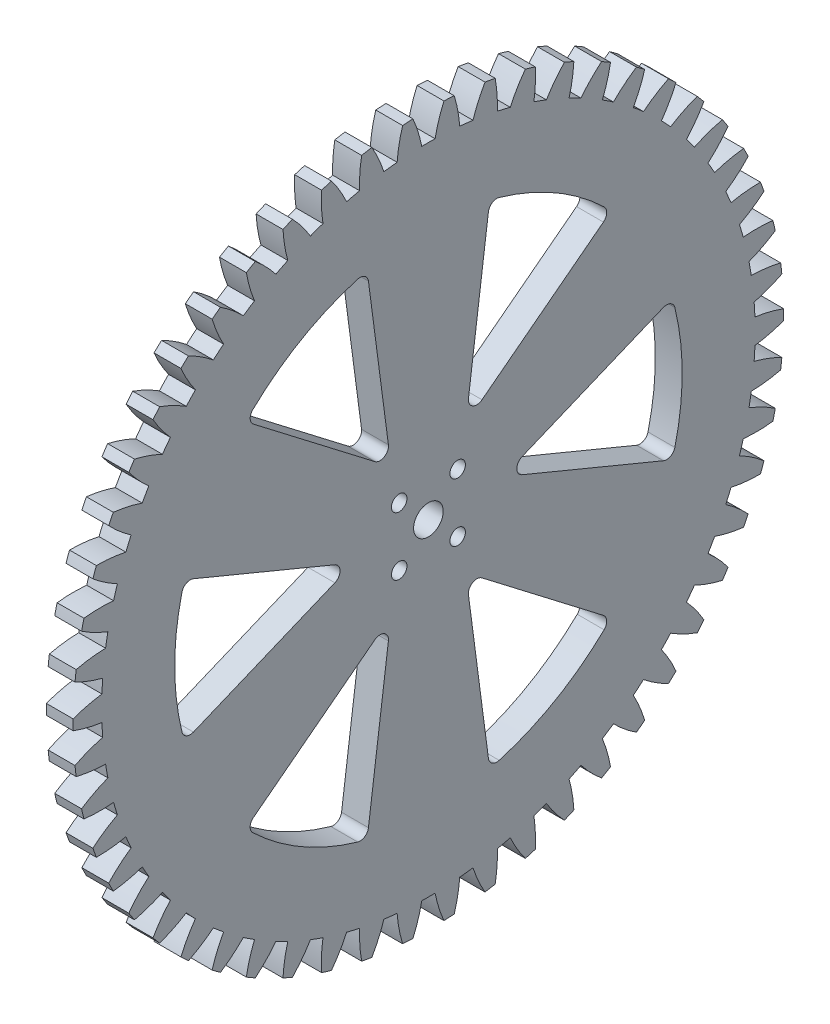
SolidWorks part; units mm, degrees
ref_plane "Plane1" through (0, 0, 0) normal (0, 0, 1) x (1, 0, 0)
ref_plane "Plane2" through (0, 0, 0) normal (0, 1, 0) x (1, 0, 0)
ref_plane "Plane3" through (0, 0, 0) normal (1, 0, 0) x (0, 0, -1)
sketch "HoldingSke" plane through (0, 0, 0) normal (0, 1, 0) x (1, 0, 0)
  line L0 (0, 0) -> (0.1959, -0.2697)
  line L1 (-15, 0) -> (100, 0) construction
  line L2 (0, 0) -> (-2.1039, 2.3779)
  line L3 (0, 0) -> (-11.863, 4.5341)
  line L4 (0, 0) -> (5.0761, 6.9867)
  line L5 (0, 0) -> (-46.8476, -17.4728)
  line L6 (0, 0) -> (-5.2639, -3.5516)
  line L7 (-2.1039, 2.3779) -> (8.6586, 51.2059)
  line L8 (-76.2, 54.61) -> (-75.2, 54.61)
  line L9 (-67.7845, 28.3722) -> (-49.3413, 33.142)
  line L10 (-76.2, 71.12) -> (104.1128, 71.12)
  line L11 (0, 0) -> (-6.35, 0)
  line L12 (-76.2, 101.6) -> (-76.093, 101.6)
  line L13 (24.9733, 27.94) -> (52.9518, 28.4284)
  line L14 (24.9733, 27.94) -> (24.9743, 27.94)
  line L15 (24.9733, 27.94) -> (100.4006, 29.5858)
  line L16 (-63.627, -3) -> (-12.827, -3)
  circle A0 centre (0, 0) radius 3.5
  circle A1 centre (0, 0) radius 37.5
  circle A2 centre (0, 0) radius 37.5
  circle A3 centre (0, 0) radius 3.5
  dimension "Num_teeth" = 54
  dimension "Pitch_radius" = 180.3128
  dimension "Width" = 6.35
  dimension "Thickness" = 6.35
sketch "BasProSke" plane through (0, 0, 0) normal (0, 1, 0) x (1, 0, 0)
  line L0 (-10, 0) -> (60, 0) construction
  line L1 (0, 0) -> (0, 84)
  line L2 (0, 0) -> (6.35, 0)
  line L3 (6.35, 0) -> (6.35, 84)
  line L4 (6.35, 84) -> (0, 84)
  dimension "Thickness" = 6.35
  dimension "Diameter" = 168
revolve "Base-Revolve" add sketch "BasProSke" angle 360 about L0
sketch "TooCutSke" plane through (0, 0, 0) normal (1, 0, 0) x (0, 0, -1)
  line L1 (0, 0) -> (0, 107) construction
  line L2 (0, 0) -> (-2.5431, 80.9601) construction
  line L3 (0, 0) -> (-9.4161, 161.6679) construction
  line L4 (-2.5431, 80.9601) -> (-4.708, 80.834) construction
  arc A0 (1.5754, 77.2329) -> (-1.5754, 77.2329) centre (0, 0) ccw
  arc A1 (3.6761, 83.9449) -> (-3.6761, 83.9449) centre (0, 0) ccw
  circle A2 centre (0, 0) radius 81 construction
  circle A3 centre (0, 0) radius 78.42 construction
  arc A4 (-1.5754, 77.2329) -> (-3.6761, 83.9449) centre (-33.364, 70.9685) ccw
  arc A5 (3.6761, 83.9449) -> (1.5754, 77.2329) centre (33.364, 70.9685) ccw
extrude "ToothCut" cut sketch "TooCutSke" along normal through all
fillet "Breaks" [suppressed] radius 0.06 tangent propagation no
fillet "RootFillets" [suppressed] radius 0.751
pattern_circular "TeethCuts" count 54 every 6.667 about axis through (-10, 0, 0) along (1, 0, 0) of "ToothCut", "RootFillets", "Breaks"
sketch "HubNeaOneSke" plane through (0, 0, 0) normal (-1, 0, 0) x (0, 0, 1)
  circle A0 centre (0, 0) radius 37.5
  dimension "Diameter" = 75
extrude "HubNearOne" [suppressed] add sketch "HubNeaOneSke" along normal blind 43.6501
sketch "HubNeaBotSke" plane through (0, 0, 0) normal (-1, 0, 0) x (0, 0, 1)
  circle A0 centre (0, 0) radius 37.5
  dimension "Diameter" = 75
extrude "HubNearBoth" [suppressed] add sketch "HubNeaBotSke" along normal blind 21.825
ref_plane "FarPln" through (6.35, 0, 0) normal (1, 0, 0) x (0, 0, -1)
sketch "HubFarSke" plane through (6.35, 0, 0) normal (1, 0, 0) x (0, 0, -1)
  circle A0 centre (0, 0) radius 37.5
  dimension "Diameter" = 75
extrude "HubFar" [suppressed] add sketch "HubFarSke" along normal blind 21.825
sketch "BorSke" plane through (0, 0, 0) normal (1, 0, 0) x (0, 0, -1)
  circle A0 centre (0, 0) radius 3.5
  dimension "Diameter" = 7
extrude "Bore" cut sketch "BorSke" along normal mid plane 100.0001
sketch "KeySke" plane through (0, 0, 0) normal (1, 0, 0) x (0, 0, -1)
  line L0 (-1, 0) -> (-1, 4.5)
  line L1 (-1, 4.5) -> (1, 4.5)
  line L2 (1, 4.5) -> (1, 0)
  line L3 (0, 0) -> (0, 34) construction
  line L4 (-1, 0) -> (1, 0)
  dimension "Width" = 2
extrude "Keyway" [suppressed] cut sketch "KeySke" along normal mid plane 100.0001
pattern_circular "Keyway2" [suppressed] count 2 every 90 about axis through (-10, 0, 0) along (1, 0, 0) reverse direction yes
sketch "Esquisse1" plane through (0, 0, 0) normal (-1, 0, 0) x (0, 0, 1)
  circle A0 centre (6.9148, 6.9148) radius 1.83
  point P2 (6.9148, 6.9148)
  dimension "D1" = 3.66
extrude "Enlèv. mat.-Extru.1" cut sketch "Esquisse1" against normal up to next
pattern_circular "Répétition circulaire1" count 4 every 90 about axis through (0, 0, 0) along (-1, 0, 0) of "Enlèv. mat.-Extru.1"
sketch "Esquisse2" plane through (0, 0, 0) normal (-1, 0, 0) x (0, 0, 1)
  line L0 (17.667, 0) -> (57.667, 16.5685)
  line L1 (17.667, 0) -> (57.667, -16.5685)
  line L2 (50, 0) -> (-50, 0) construction
  arc A0 (57.667, -16.5685) -> (57.667, 16.5685) centre (0, 0) ccw
  point P5 (16.15, 0)
  point P7 (11.6683, 0)
  point P10 (50.8815, -40.4484)
  point P11 (60.648, -23.3842)
  dimension "D2" = 120
  dimension "D1" = 40
  dimension "D3" = 45
extrude "Enlèv. mat.-Extru.2" cut sketch "Esquisse2" against normal up to next
fillet "Congé1" radius 2 3 edges at (3.175, 0, 17.667) (3.175, -16.5685, 57.667) (3.175, 16.5685, 57.667)
pattern_circular "Répétition circulaire2" count 6 over 360 about axis through (0, 0, 0) along (-1, 0, 0) of "Enlèv. mat.-Extru.2", "Congé1"
equation "' \"Module@HoldingSke\" = 6.35"
equation "' \"Num_teeth@HoldingSke\" = 12"
equation "' \"Ap@HoldingSke\" =  20"
equation "' \"Ap@HoldingSke\" = 20"
equation "' \"Width@HoldingSke\" = 0.5 * 25.4"
equation "' \"Hub_dia@HoldingSke\"= 1 * 25.4"
equation "' \"Hub_dia@HoldingSke\" = 1 * 25.4"
equation "' \"Overall_len@HoldingSke\" = 1.0 * 25.4"
equation "' \"Bore@HoldingSke\" = 0.75 * 25.4"
equation "' \"T_dim@HoldingSke\" = 0.1 * 25.4"
equation "' \"Width@KeySke\" = 0.25 * 25.4"
equation "' \"Show_teeth@HoldingSke\" = 13"
equation "' \"Backlash@HoldingSke\" = 0.009 * 25.4"
equation "' \"Addendum_fac@HoldingSke\" = 1.0"
equation "' \"Dedendum_fac@HoldingSke\" = 1.25"
equation "' \"Dedendum_add@HoldingSke\" = 0.00005 * 25.4"
equation "' \"Clearance_fac@HoldingSke\" = 0.25"
equation "\"Pitch@HoldingSke\" = 1 / \"Module@HoldingSke\""
equation "\"Overcut_dia@TooCutSke\" = (\"Num_teeth@HoldingSke\" + 2 * \"Addendum_fac@HoldingSke\") / \"Pitch@HoldingSke\" + 0.002 * 25.4"
equation "\"Pitch_dia@TooCutSke\" = \"Num_teeth@HoldingSke\" / \"Pitch@HoldingSke\""
equation "\"Base_dia@TooCutSke\" = \"Num_teeth@HoldingSke\" / \"Pitch@HoldingSke\" * cos((\"Ap@HoldingSke\"  * 3.14159265 / 180))"
equation "\"Root_dia@TooCutSke\" = (\"Num_teeth@HoldingSke\" + 2) / \"Pitch@HoldingSke\" - 2 * (\"Addendum_fac@HoldingSke\" + \"Dedendum_fac@HoldingSke\") / \"Pitch@HoldingSke\" - \"Dedendum_add@HoldingSke\" * 2"
equation "\"Half_ang@TooCutSke\" = 180 / \"Num_teeth@HoldingSke\""
equation "\"Half_CT@TooCutSke\" = \"Num_teeth@HoldingSke\" / \"Pitch@HoldingSke\" * sin((3.14159265 / 2 / \"Num_teeth@HoldingSke\")) / 2 - 7 * \"Backlash@HoldingSke\" / 4"
equation "\"Flank_rad@TooCutSke\" = \"Num_teeth@HoldingSke\" / \"Pitch@HoldingSke\" / 5"
equation "\"Radius@RootFillets\" = \"Clearance_fac@HoldingSke\" / \"Pitch@HoldingSke\" + \"Dedendum_add@HoldingSke\""
equation "\"Break_rad@Breaks\" = 0.02 / \"Pitch@HoldingSke\""
equation "\"Thickness@HoldingSke\" = \"Width@HoldingSke\""
equation "\"OAL@HoldingSke\" = \"Thickness@HoldingSke\""
equation "\"MHD@HoldingSke\" = (\"Num_teeth@HoldingSke\" + 2) / \"Pitch@HoldingSke\" - 2 * (\"Addendum_fac@HoldingSke\" + \"Dedendum_fac@HoldingSke\")  / \"Pitch@HoldingSke\" - \"Dedendum_add@HoldingSke\" * 2"
equation "\"MBD@HoldingSke\" = (\"Num_teeth@HoldingSke\" + 2) / \"Pitch@HoldingSke\" - 2 * (\"Addendum_fac@HoldingSke\" + \"Dedendum_fac@HoldingSke\")  / \"Pitch@HoldingSke\" - \"Dedendum_add@HoldingSke\" * 2 - 0.002 * 25.4"
equation "\"MHD@HoldingSke\" = ((sgn( \"MHD@HoldingSke\" - \"Hub_dia@HoldingSke\" )-1)*( \"MHD@HoldingSke\" - \"Hub_dia@HoldingSke\" ))/-2+ \"Hub_dia@HoldingSke\""
equation "\"MBD@HoldingSke\" = ((sgn( \"MBD@HoldingSke\" - \"Bore@HoldingSke\" )-1)*( \"MBD@HoldingSke\" - \"Bore@HoldingSke\" ))/-2+ \"Bore@HoldingSke\""
equation "\"OAL@HoldingSke\" = ((sgn( \"OAL@HoldingSke\" - \"Overall_len@HoldingSke\" )+1)*( \"OAL@HoldingSke\" - \"Overall_len@HoldingSke\" ))/2 + \"Overall_len@HoldingSke\" + 0.000002 * 25.4"
equation "\"Num_teeth@TeethCuts\" = int( \"Show_teeth@HoldingSke\" ) + 1"
equation "\"Num_teeth@TeethCuts\" = ((sgn( \"Num_teeth@TeethCuts\" - \"Num_teeth@HoldingSke\" )-1)*( \"Num_teeth@TeethCuts\" - \"Num_teeth@HoldingSke\" ))/-2+ \"Num_teeth@HoldingSke\""
equation "\"Num_teeth@TeethCuts\" = ((sgn( \"Num_teeth@TeethCuts\" - 2.0)+1)*( \"Num_teeth@TeethCuts\" - 2.0))/2 +2.0"
equation "\"Angle@TeethCuts\" = 360.0 / \"Num_teeth@HoldingSke\""
equation "\"Diameter@BasProSke\" = (\"Num_teeth@HoldingSke\" + 2 * \"Addendum_fac@HoldingSke\") / \"Pitch@HoldingSke\""
equation "\"Thickness@BasProSke\"  = \"Thickness@HoldingSke\""
equation "' \"Fillet_rad@BasProSke\" =  \"Thickness@HoldingSke\" * 0.05"
equation "' \"Fillet_rad@BasProSke\" = \"Thickness@HoldingSke\" * 0.05"
equation "\"MHD@HoldingSke\" = ((sgn( \"MHD@HoldingSke\" - \"Root_dia@TooCutSke\" )-1)*( \"MHD@HoldingSke\" - \"Root_dia@TooCutSke\" ))/-2+ \"Root_dia@TooCutSke\""
equation "\"Diameter@HubNeaOneSke\" = \"MHD@HoldingSke\""
equation "\"Length@HubNearOne\" = \"OAL@HoldingSke\" - \"Thickness@BasProSke\""
equation "\"Diameter@HubNeaBotSke\" = \"MHD@HoldingSke\""
equation "\"Length@HubNearBoth\" = ( \"OAL@HoldingSke\" - \"Thickness@BasProSke\" ) / 2.0"
equation "\"Thickness@FarPln\" = \"Thickness@BasProSke\""
equation "\"Diameter@HubFarSke\" = \"MHD@HoldingSke\""
equation "\"Length@HubFar\" = ( \"OAL@HoldingSke\" - \"Thickness@BasProSke\" ) / 2.0"
equation "\"Diameter@BorSke\" = \"MBD@HoldingSke\""
equation "\"D1@Bore\" = \"OAL@HoldingSke\" * 2.0"
equation "\"D1@Keyway\" = \"OAL@HoldingSke\" * 2.0"
equation "\"Offset@KeySke\" = \"T_dim@HoldingSke\" + \"MBD@HoldingSke\" / 2.0"
